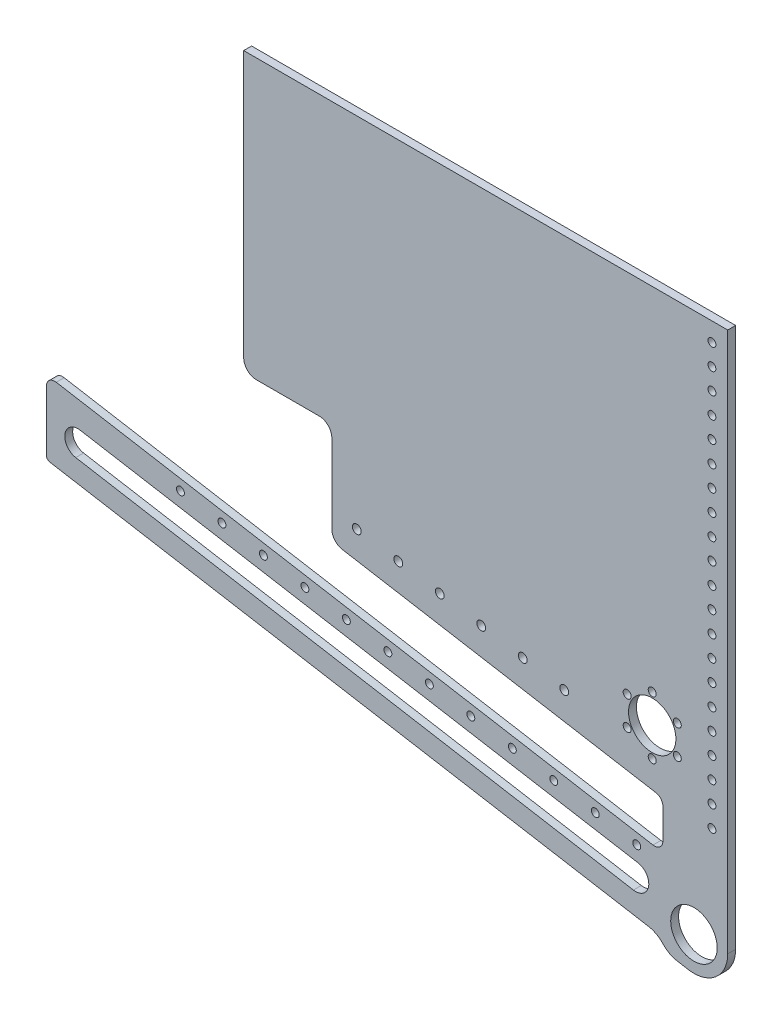
SolidWorks part; units mm, degrees
material "Polypropylene"
ref_plane "Front Plane" through (0, 0, 0) normal (0, 0, 1) x (1, 0, 0)
ref_plane "Top Plane" through (0, 0, 0) normal (0, 1, 0) x (1, 0, 0)
ref_plane "Right Plane" through (0, 0, 0) normal (1, 0, 0) x (0, 0, -1)
sketch "Sketch1" plane through (0, 0, 0) normal (0, 0, 1) x (1, 0, 0)
  line L0 (19.05, 0) -> (19.05, -76.2) construction
  line L1 (0, 19.05) -> (-57.15, 19.05) construction
  line L2 (19.05, -155.575) -> (168.9894, -155.575) construction
  line L3 (0, -95.25) -> (-57.15, -95.25) construction
  line L4 (-57.15, -95.25) -> (-57.15, 19.05) construction
  line L5 (168.9894, 7.239) -> (168.9894, -18.161) construction
  line L6 (168.9894, -18.161) -> (168.9894, -155.575) construction
  line L7 (168.9894, 7.239) -> (143.6189, 6.0141) construction
  line L8 (143.6189, 6.0141) -> (19.05, 0) construction
  line L9 (165.5424, -12.8509) -> (158.8645, -11.7052)
  line L10 (189.3729, 7.239) -> (189.3729, 131.5601)
  line L12 (197.5644, 110.4886) -> (197.5644, -33.1911) construction
  line L16 (-221.8076, 98.3842) -> (-221.8076, 62.1942)
  line L17 (133.7924, 19.9786) -> (-202.7576, 77.7234) construction
  line L18 (132.4501, 12.1554) -> (-204.0999, 69.9002)
  line L19 (135.1346, 27.8017) -> (-201.4154, 85.5465)
  line L20 (-215.8686, 103.3911) -> (107.3768, 47.929)
  line L23 (-219.6972, 59.6908) -> (141.5847, -2.2975)
  line L24 (179.8479, 131.5601) -> (179.8479, 118.8601) construction
  line L25 (179.8479, 118.8601) -> (189.3729, 118.8601) construction
  line L31 (107.3768, 47.929) -> (144.2855, 41.5963)
  line L32 (150.2246, 46.6031) -> (150.2246, 64.8314)
  line L38 (146.0036, 69.8383) -> (-43.2183, 102.3047)
  line L40 (189.3729, 131.5601) -> (189.3729, 333.3075)
  line L42 (-102.7271, 172.6972) -> (-102.7271, 333.3075)
  line L43 (-102.7271, 333.3075) -> (189.3729, 333.3075)
  line L48 (-49.5497, 109.815) -> (-49.5497, 157.4572)
  line L49 (-57.1697, 165.0772) -> (-95.1071, 165.0772)
  line L50 (-40.7554, 66.9026) -> (-34.4671, 117.3119) construction
  line L51 (34.3472, 54.0166) -> (40.7189, 104.4154) construction
  line L52 (-34.4671, 117.3119) -> (40.7189, 104.4154) construction
  arc A0 (19.05, 0) -> (0, 19.05) centre (0, 0) ccw construction
  arc A1 (19.05, -76.2) -> (0, -95.25) centre (0, -76.2) cw construction
  circle A2 centre (168.9894, 7.239) radius 14.0335
  arc A3 (168.9894, -18.161) -> (143.6189, 6.0141) centre (168.9894, 7.239) ccw construction
  arc A4 (165.5424, -12.8509) -> (189.3729, 7.239) centre (168.9894, 7.239) ccw
  arc A5 (132.4501, 12.1554) -> (135.1346, 27.8017) centre (133.7924, 19.9786) ccw
  arc A6 (-201.4154, 85.5465) -> (-204.0999, 69.9002) centre (-202.7576, 77.7234) ccw
  circle A8 centre (179.8479, 118.8601) radius 2.3813
  circle A9 centre (179.8479, 106.1601) radius 2.3813
  circle A10 centre (179.8479, 93.4601) radius 2.3813
  circle A11 centre (179.8479, 80.7601) radius 2.3813
  circle A12 centre (179.8479, 68.0601) radius 2.3813
  circle A15 centre (109.4497, 41.1306) radius 2.3813
  circle A16 centre (84.4155, 45.4259) radius 2.3812
  circle A17 centre (59.3813, 49.7212) radius 2.3813
  circle A18 centre (34.3472, 54.0166) radius 2.3813
  circle A19 centre (9.313, 58.3119) radius 2.3813
  circle A20 centre (-15.7212, 62.6072) radius 2.3812
  circle A21 centre (-40.7554, 66.9026) radius 2.3813
  circle A22 centre (-65.7896, 71.1979) radius 2.3813
  circle A23 centre (-90.8237, 75.4932) radius 2.3812
  circle A24 centre (-115.8579, 79.7886) radius 2.3813
  circle A25 centre (-140.8921, 84.0839) radius 2.3812
  circle A28 centre (134.4839, 36.8353) radius 2.3813
  arc A31 (-219.6972, 59.6908) -> (-221.8076, 62.1942) centre (-219.2676, 62.1942) cw
  arc A34 (158.8645, -11.7052) -> (150.2246, -7.0013) centre (161.4417, 3.3154) cw
  circle A39 centre (143.8098, 103.921) radius 21.9964 construction
  circle A40 centre (143.8098, 103.921) radius 14.2875
  circle A41 centre (143.8098, 103.921) radius 17.4625 construction
  circle A42 centre (143.8098, 121.3835) radius 2.413
  circle A43 centre (158.9328, 112.6523) radius 2.413
  circle A44 centre (158.9328, 95.1898) radius 2.413
  circle A45 centre (143.8098, 86.4585) radius 2.413
  circle A46 centre (128.6869, 95.1898) radius 2.413
  circle A47 centre (128.6869, 112.6523) radius 2.413
  arc A48 (141.5847, -2.2975) -> (150.2246, -7.0013) centre (139.0075, -17.318) cw
  arc A49 (144.2855, 41.5963) -> (150.2246, 46.6031) centre (145.1446, 46.6031) ccw
  arc A53 (-221.8076, 98.3842) -> (-215.8686, 103.3911) centre (-216.7276, 98.3842) cw
  arc A55 (150.2246, 64.8314) -> (146.0036, 69.8383) centre (145.1446, 64.8314) ccw
  circle A57 centre (179.8479, 131.5601) radius 2.3813
  circle A58 centre (179.8479, 144.2601) radius 2.3813
  circle A59 centre (179.8479, 156.9601) radius 2.3812
  circle A60 centre (179.8479, 169.6601) radius 2.3813
  circle A61 centre (179.8479, 182.3601) radius 2.3813
  circle A62 centre (179.8479, 195.0601) radius 2.3813
  circle A63 centre (179.8479, 207.7601) radius 2.3813
  circle A64 centre (179.8479, 220.4601) radius 2.3812
  circle A65 centre (179.8479, 233.1601) radius 2.3813
  circle A66 centre (179.8479, 245.8601) radius 2.3813
  circle A67 centre (179.8479, 258.5601) radius 2.3813
  circle A68 centre (179.8479, 271.2601) radius 2.3813
  circle A69 centre (179.8479, 283.9601) radius 2.3812
  circle A70 centre (179.8479, 296.6601) radius 2.3812
  circle A71 centre (179.8479, 309.3601) radius 2.3813
  circle A72 centre (179.8479, 322.0601) radius 2.3813
  arc A79 (-43.2183, 102.3047) -> (-49.5497, 109.815) centre (-41.9297, 109.815) cw
  arc A80 (-102.7271, 172.6972) -> (-95.1071, 165.0772) centre (-95.1071, 172.6972) ccw
  arc A81 (-49.5497, 157.4572) -> (-57.1697, 165.0772) centre (-57.1697, 157.4572) ccw
  circle A84 centre (-9.4327, 113.0178) radius 2.667
  circle A86 centre (15.6017, 108.7237) radius 2.667
  circle A88 centre (40.636, 104.4296) radius 2.667
  circle A90 centre (65.6704, 100.1355) radius 2.667
  circle A92 centre (90.7048, 95.8414) radius 2.667
  circle A94 centre (-34.4671, 117.3119) radius 2.667
  point P24 (-34.4826, 48.851)
  point P51 (-221.8076, 53.6101)
  point P92 (143.8191, 3.8303)
  point P95 (150.6057, -10.2881)
  point P107 (-221.8076, 104.4101)
  point P118 (143.8098, 103.921)
  dimension "D1" = 19.05
  dimension "D4" = 19.05
  dimension "D6" = 28.067
  dimension "D7" = 50.8
  dimension "D10" = 6.35
  dimension "D13" = 28.575
  dimension "D15" = 7.9375
  dimension "D21" = 7.62
  dimension "D23" = 5
  dimension "D24" = 4.7625
  dimension "D25" = 5.08
  dimension "D26" = 2.54
  dimension "D27" = 15.24
  dimension "D28" = 12.7
  dimension "D30" = 5.08
  dimension "D31" = 43.9928
  dimension "D32" = 34.925
  dimension "D33" = 50.8
  dimension "D34" = 4.826
  dimension "D35" = 6
  dimension "D19" = 28.575
  dimension "D2" = 155.575
  dimension "D3" = 76.2
  dimension "D5" = 114.3
  dimension "D8" = 137.414
  dimension "D9" = 124.714
  dimension "D11" = 12.5
  dimension "D12" = 387.35
  dimension "D14" = 50.8
  dimension "D16" = 19.05
  dimension "D17" = 19.05
  dimension "D18" = 336.55
  dimension "D20" = 2
  dimension "D22" = 12.7
  dimension "D29" = 12.7
  dimension "D37" = 292.1
  dimension "D36" = 17
extrude "Boss-Extrude1" add sketch "Sketch1" along normal blind 4.7625
sketch "Sketch2" plane through (0, 0, 4.7625) normal (0, 0, 1) x (1, 0, 0)
  line L0 (-220.5687, 53.4619) -> (-220.7855, 56.0635)
  line L1 (-221.0377, 56.3386) -> (-222.0622, 56.5143)
  line L2 (-222.3916, 56.3391) -> (-223.4633, 53.9586)
  line L3 (-223.5225, 53.9043) -> (-223.5182, 53.9293) construction
  line L4 (-221.5499, 56.4265) -> (-222.0267, 53.6477) construction
  line L5 (-220.5266, 54.7046) -> (-223.0887, 55.1442) construction
  line L6 (158.8645, -11.7052) -> (165.5424, -12.8509) construction
  line L7 (-222.9409, 55.1189) -> (-223.1934, 53.6477) construction
  line L8 (-220.6744, 54.73) -> (-220.8601, 53.6477) construction
  line L11 (-220.5309, 53.391) -> (-223.5225, 53.9043)
  line L13 (-220.5266, 53.4161) -> (-220.056, 53.3353)
  line L14 (-220.056, 53.3353) -> (-220.0603, 53.3103)
  line L15 (-220.0603, 53.3103) -> (-220.5309, 53.391)
  line L16 (-220.5309, 53.391) -> (-220.5266, 53.4161) construction
  line L17 (-223.9889, 54.0101) -> (-223.9931, 53.9851)
  line L18 (-223.9931, 53.9851) -> (-223.5225, 53.9043)
  line L19 (-223.5182, 53.9293) -> (-223.9889, 54.0101)
  line L21 (-221.8076, 98.3842) -> (-221.8076, 62.1942) construction
  arc A0 (-222.0622, 56.5143) -> (-222.3916, 56.3391) centre (-222.1137, 56.2139) ccw
  arc A1 (-220.7855, 56.0635) -> (-221.0377, 56.3386) centre (-221.0892, 56.0382) ccw
  arc A2 (-223.5182, 53.9293) -> (-223.4633, 53.9586) centre (-223.5096, 53.9794) ccw
  arc A3 (-220.5687, 53.4619) -> (-220.5266, 53.4161) centre (-220.518, 53.4661) ccw
  point P6 (-221.8076, 54.9244)
  dimension "D1" = 0.0254
  dimension "Root_fillet" = 0.3048
  dimension "Break_rad" = 0.0508
  dimension "Gap_width" = 2.2997
  dimension "Dedendum" = 1.524
  dimension "Addendum_plus" = 1.2954
  dimension "Pressure_angle" = 14.5
  dimension "D2" = 0.4775
